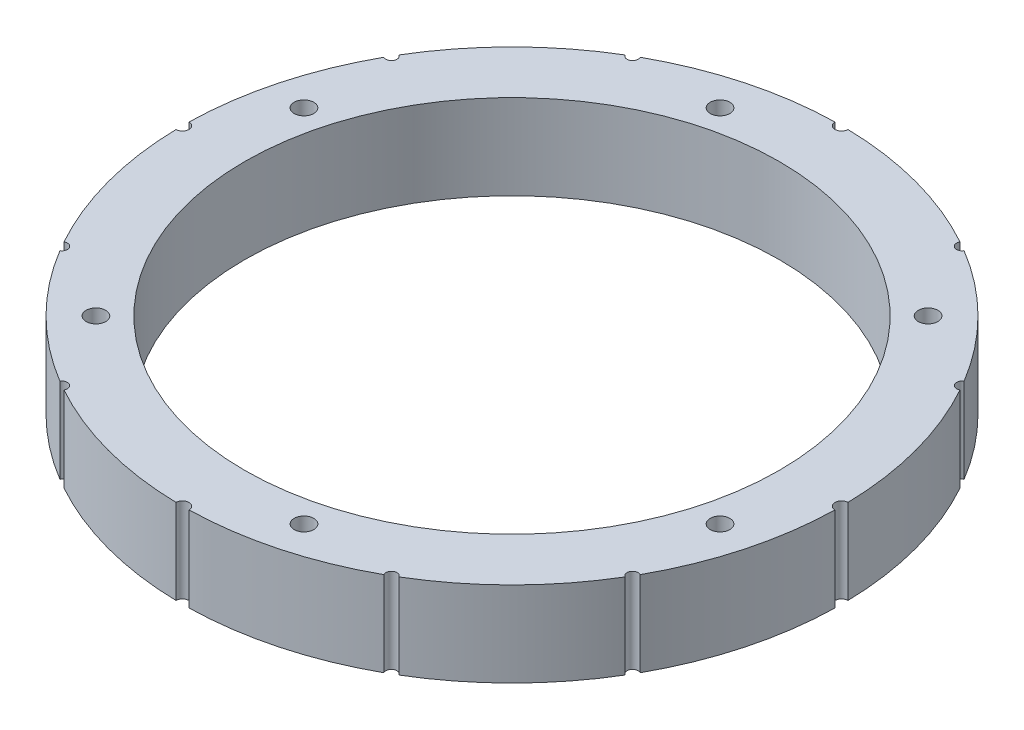
SolidWorks part; units mm, degrees
ref_plane "前视基准面" through (0, 0, 0) normal (0, 0, 1) x (1, 0, 0)
ref_plane "上视基准面" through (0, 0, 0) normal (0, 1, 0) x (1, 0, 0)
ref_plane "右视基准面" through (0, 0, 0) normal (1, 0, 0) x (0, 0, -1)
sketch "草图1" plane through (0, 0, 0) normal (0, 1, 0) x (1, 0, 0)
  circle A0 centre (0, 0) radius 40.9
  circle A1 centre (0, 0) radius 50.4
  dimension "D1" = 81.8
  dimension "D2" = 100.8
extrude "凸台-拉伸1" add sketch "草图1" against normal blind 13
sketch "草图2" plane through (0, -13, 0) normal (0, -1, 0) x (1, 0, 0)
  line L0 (0, -75.2808) -> (0, 56.4382) construction
  circle A0 centre (0, 50.4) radius 1
  circle A1 centre (0, 0) radius 50.4 construction
  circle A2 centre (50.4, 0) radius 1
  circle A3 centre (0, -50.4) radius 1
  circle A4 centre (-50.4, 0) radius 1
  circle A5 centre (-25.2, 43.6477) radius 0.85
  circle A6 centre (25.2, 43.6477) radius 0.85
  circle A7 centre (43.6477, 25.2) radius 0.85
  circle A8 centre (43.6477, -25.2) radius 0.85
  circle A9 centre (25.2, -43.6477) radius 0.85
  circle A10 centre (-25.2, -43.6477) radius 0.85
  circle A11 centre (-43.6477, -25.2) radius 0.85
  circle A12 centre (-43.6477, 25.2) radius 0.85
  point P14 (0, 0)
  point P33 (0, 0)
  dimension "D1" = 2
  dimension "D3" = 1.7
  dimension "D4" = 30
  dimension "D2" = 4
  dimension "D5" = 4
extrude "切除-拉伸1" cut sketch "草图2" against normal blind 13
sketch "草图3" plane through (0, 0, 0) normal (0, 1, 0) x (1, 0, 0)
  line L0 (0, -59.1889) -> (0, 55.0049) construction
  line L1 (-11.6469, 43.4667) -> (0, 0) construction
  circle A0 centre (-11.6469, 43.4667) radius 1.5
  circle A2 centre (0, 0) radius 40.9 construction
  point P21 (0, 0)
  dimension "D1" = 3
  dimension "D2" = 45
  dimension "D3" = 15
extrude "切除-拉伸2" cut sketch "草图3" against normal blind 5
cosmetic thread "装饰螺纹线1" parameters "D2"=4
sketch "草图4" plane through (0, 0, 0) normal (1, 0, 0) x (0, 0, -1)
  line L0 (0, 10.2914) -> (0, -21.6359) construction
pattern_circular "阵列(圆周)1" count 6 over 360 about axis through (0, 10.2914, 0) along (0, -1, 0) of "切除-拉伸2"
